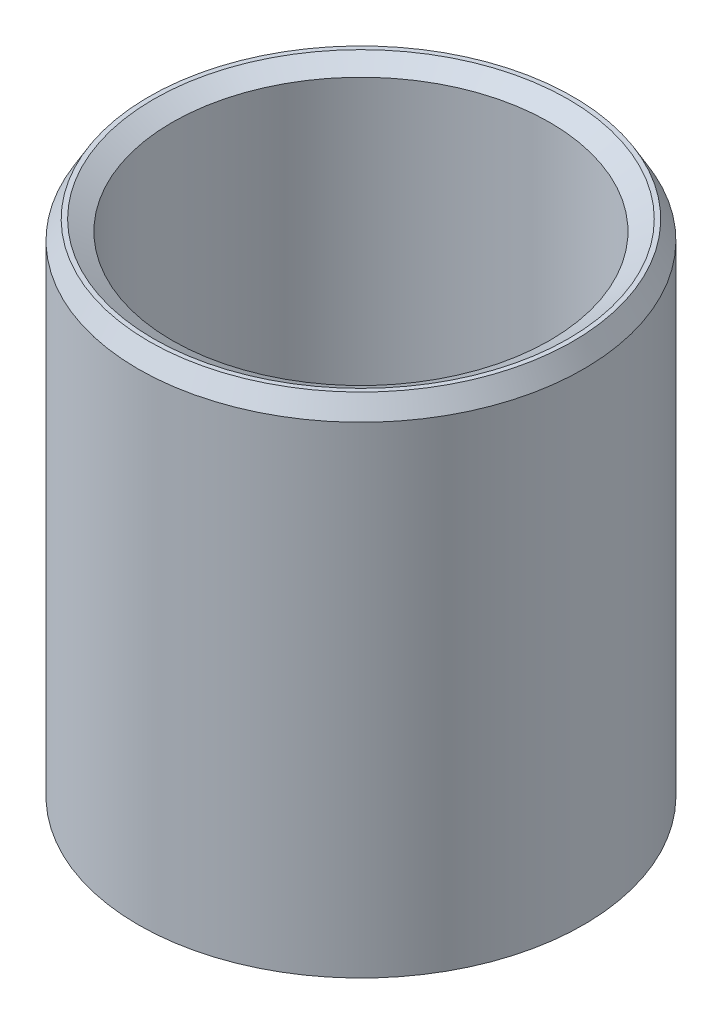
SolidWorks part; units mm, degrees
ref_plane "Front Plane" through (0, 0, 0) normal (0, 0, 1) x (1, 0, 0)
ref_plane "Top Plane" through (0, 0, 0) normal (0, 1, 0) x (1, 0, 0)
ref_plane "Right Plane" through (0, 0, 0) normal (1, 0, 0) x (0, 0, -1)
sketch "Sketch1" plane through (0, 0, 0) normal (0, 1, 0) x (1, 0, 0)
  circle A0 centre (0, 0) radius 42.5
  dimension "SLEEVE_OD" = 85
extrude "Boss-Extrude1" add sketch "Sketch1" along normal blind 97.4391
sketch "Sketch2" plane through (0, 0, 0) normal (0, 1, 0) x (1, 0, 0)
  circle A0 centre (0, 0) radius 36.0372
  dimension "BORE_D" = 72.0743
extrude "Cut-Extrude1" cut sketch "Sketch2" along normal through all
chamfer "Chamfer1" distance 3.5468 angle 30 4 edges at (0, 97.4391, 36.0372) (0, 0, 36.0372) (0, 0, 42.5) (0, 97.4391, 42.5) first distance on face at (0, 97.4391, 36.0372) first distance on face at (0, 0, 36.0372) first distance on face at (0, 97.4391, 42.5)
